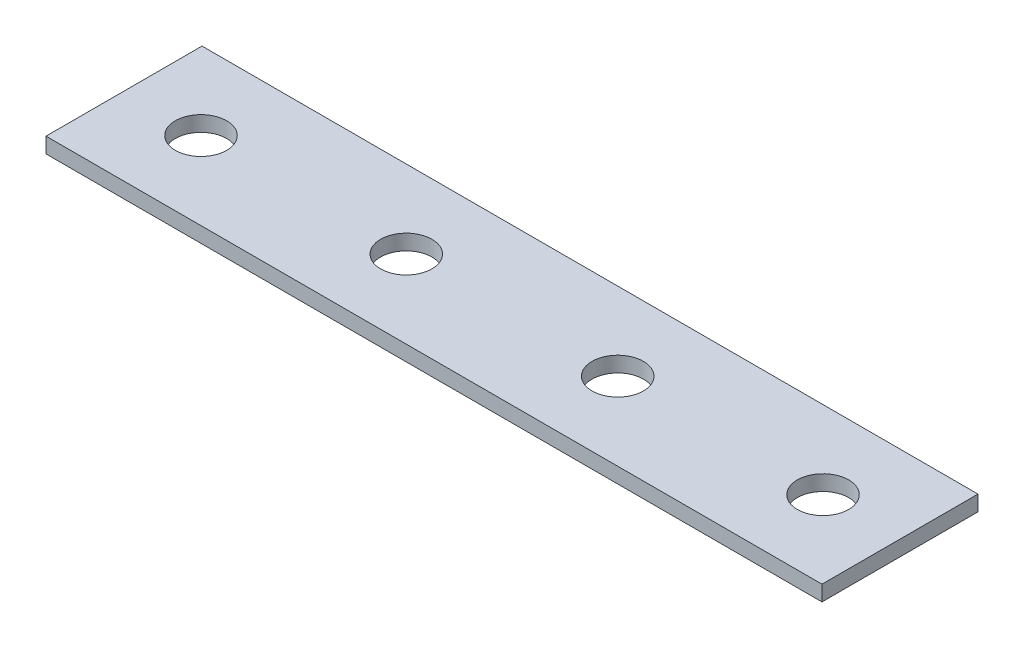
SolidWorks part; units mm, degrees
ref_plane "Front plane" through (0, 0, 0) normal (0, 0, 1) x (1, 0, 0)
ref_plane "Top plane" through (0, 0, 0) normal (0, 1, 0) x (1, 0, 0)
ref_plane "Right plane" through (0, 0, 0) normal (1, 0, 0) x (0, 0, -1)
ref_axis "Axis X" through (0, 0, 0) along (1, 0, 0)
ref_axis "Axis Y" through (0, 0, 0) along (0, 1, 0)
ref_axis "Axis Z" through (0, 0, 0) along (0, 0, 1)
sketch "Sketch1" plane through (0, 0, 0) normal (0, 1, 0) x (1, 0, 0)
  line L0 (0, 7.6) -> (0, -7.6) construction
  line L1 (37.8, 7.6) -> (-37.8, 7.6)
  line L2 (37.8, 7.6) -> (37.8, -7.6)
  line L3 (37.8, -7.6) -> (-37.8, -7.6)
  line L4 (-37.8, 7.6) -> (-37.8, -7.6)
  line L5 (37.8, 7.6) -> (-37.8, -7.6) construction
  line L6 (37.8, -7.6) -> (-37.8, 7.6) construction
  line L7 (-37.8, 0) -> (37.8, 0) construction
  circle A0 centre (-30.3, 0) radius 2.5
  circle A2 centre (-10.3, 0) radius 2.5
  circle A3 centre (10.3, 0) radius 2.5
  circle A4 centre (30.3, 0) radius 2.5
  point P0 (0, 0)
  dimension "D4" = 5
  dimension "D5" = 5
  dimension "D1" = 15.2
  dimension "D2" = 75.6
  dimension "D3" = 7.5
  dimension "D6" = 20
extrude "Extrude1" add sketch "Sketch1" along normal blind 1.5
equation "\"D5@Sketch1\"=\"D4@Sketch1\""
equation "\"D6@Sketch1\"=20"
